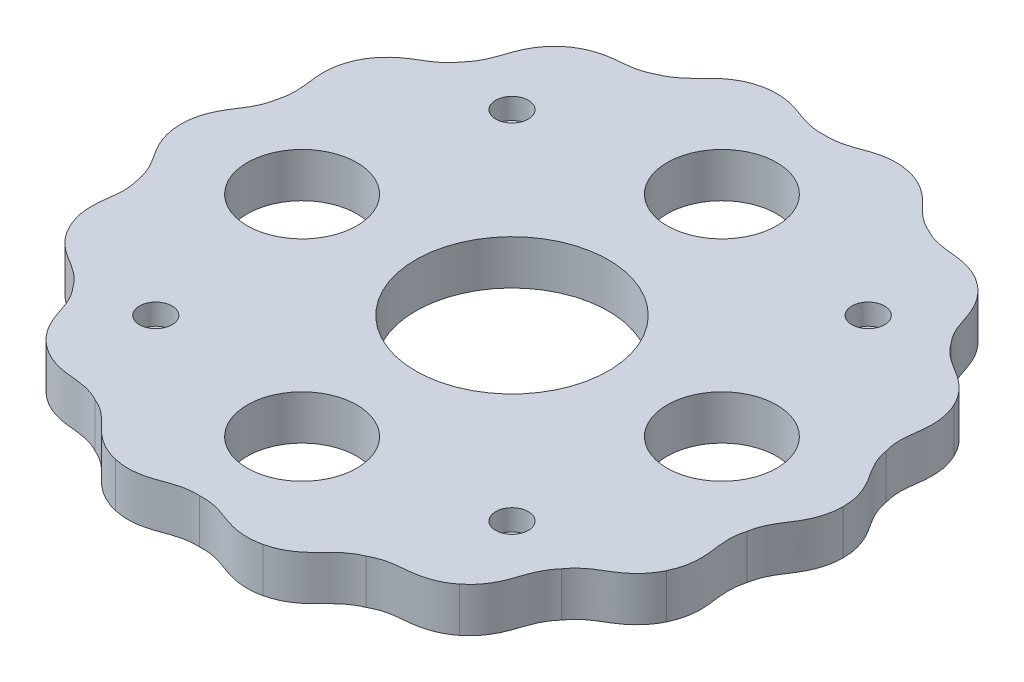
SolidWorks part; units mm, degrees
ref_plane "Front Plane" through (0, 0, 0) normal (0, 0, 1) x (1, 0, 0)
ref_plane "Top Plane" through (0, 0, 0) normal (0, 1, 0) x (1, 0, 0)
ref_plane "Right Plane" through (0, 0, 0) normal (1, 0, 0) x (0, 0, -1)
sketch "Sketch1" plane through (0, 0, 0) normal (0, 1, 0) x (1, 0, 0)
  line L0 (0, 0) -> (37.5, 0) construction
  line L1 (0, 0) -> (37.4807, 1.2019) construction
  line L2 (0, 0) -> (37.423, 2.4026) construction
  line L3 (0, 0) -> (37.3267, 3.6009) construction
  line L4 (0, 0) -> (37.1921, 4.7954) construction
  line L5 (0, 0) -> (37.0193, 5.985) construction
  line L6 (0, 0) -> (36.8085, 7.1684) construction
  line L7 (0, 0) -> (36.5598, 8.3445) construction
  line L8 (0, 0) -> (36.2736, 9.512) construction
  line L9 (0, 0) -> (35.95, 10.6698) construction
  line L10 (0, 0) -> (35.5896, 11.8166) construction
  line L11 (0, 0) -> (35.1926, 12.9512) construction
  line L12 (0, 0) -> (34.7594, 14.0725) construction
  line L13 (0, 0) -> (34.2905, 15.1794) construction
  line L14 (0, 0) -> (33.7863, 16.2706) construction
  line L15 (37.5, 0) -> (38.5, 0) construction
  line L16 (37.4807, 1.2019) -> (38.3521, 1.6927) construction
  line L17 (37.423, 2.4026) -> (37.9413, 3.2578) construction
  line L18 (37.3267, 3.6009) -> (37.3588, 4.6003) construction
  line L19 (37.1921, 4.7954) -> (36.7296, 5.682) construction
  line L20 (37.0193, 5.985) -> (36.1812, 6.5305) construction
  line L21 (36.8085, 7.1684) -> (35.8105, 7.2325) construction
  line L22 (36.5598, 8.3445) -> (35.5849, 8.122) construction
  line L23 (37, 0.0019) -> (37, 0)
  line L24 (33.3367, 16.052) -> (33.3358, 16.0537)
  line L25 (37, -0.0019) -> (37, 0)
  line L26 (33.3367, -16.052) -> (33.3358, -16.0537)
  line L27 (33.335, -16.0554) -> (33.3358, -16.0537)
  line L28 (23.0706, -28.9266) -> (23.0691, -28.9278)
  line L29 (23.0677, -28.9289) -> (23.0691, -28.9278)
  line L30 (8.2351, -36.0719) -> (8.2333, -36.0723)
  line L31 (8.2315, -36.0727) -> (8.2333, -36.0723)
  line L32 (-8.2315, -36.0727) -> (-8.2333, -36.0723)
  line L33 (-8.2351, -36.0719) -> (-8.2333, -36.0723)
  line L34 (-23.0677, -28.9289) -> (-23.0691, -28.9278)
  line L35 (-23.0706, -28.9266) -> (-23.0691, -28.9278)
  line L36 (-33.335, -16.0554) -> (-33.3358, -16.0537)
  line L37 (-33.3367, -16.052) -> (-33.3358, -16.0537)
  line L38 (-37, -0.0019) -> (-37, 0)
  line L39 (-37, 0.0019) -> (-37, 0)
  line L40 (-33.3367, 16.052) -> (-33.3358, 16.0537)
  line L41 (-33.335, 16.0554) -> (-33.3358, 16.0537)
  line L42 (-23.0706, 28.9266) -> (-23.0691, 28.9278)
  line L43 (-23.0677, 28.9289) -> (-23.0691, 28.9278)
  line L44 (-8.2351, 36.0719) -> (-8.2333, 36.0723)
  line L45 (-8.2315, 36.0727) -> (-8.2333, 36.0723)
  line L46 (8.2315, 36.0727) -> (8.2333, 36.0723)
  line L47 (8.2351, 36.0719) -> (8.2333, 36.0723)
  line L48 (23.0677, 28.9289) -> (23.0691, 28.9278)
  line L49 (23.0706, 28.9266) -> (23.0691, 28.9278)
  line L50 (33.335, 16.0554) -> (33.3358, 16.0537)
  line L51 (35.5, 0.0037) -> (35.5, 0)
  line L52 (31.986, 15.3995) -> (31.9844, 15.4029)
  line L53 (35.5, -0.0037) -> (35.5, 0)
  line L54 (31.986, -15.3995) -> (31.9844, -15.4029)
  line L55 (31.9828, -15.4062) -> (31.9844, -15.4029)
  line L56 (22.1368, -27.7527) -> (22.1339, -27.755)
  line L57 (22.131, -27.7573) -> (22.1339, -27.755)
  line L58 (7.9031, -34.6091) -> (7.8995, -34.6099)
  line L59 (7.8959, -34.6108) -> (7.8995, -34.6099)
  line L60 (-7.8959, -34.6108) -> (-7.8995, -34.6099)
  line L61 (-7.9031, -34.6091) -> (-7.8995, -34.6099)
  line L62 (-22.131, -27.7573) -> (-22.1339, -27.755)
  line L63 (-22.1368, -27.7527) -> (-22.1339, -27.755)
  line L64 (-31.9828, -15.4062) -> (-31.9844, -15.4029)
  line L65 (-31.986, -15.3995) -> (-31.9844, -15.4029)
  line L66 (-35.5, -0.0037) -> (-35.5, 0)
  line L67 (-35.5, 0.0037) -> (-35.5, 0)
  line L68 (-31.986, 15.3995) -> (-31.9844, 15.4029)
  line L69 (-31.9828, 15.4062) -> (-31.9844, 15.4029)
  line L70 (-22.1368, 27.7527) -> (-22.1339, 27.755)
  line L71 (-22.131, 27.7573) -> (-22.1339, 27.755)
  line L72 (-7.9031, 34.6091) -> (-7.8995, 34.6099)
  line L73 (-7.8959, 34.6108) -> (-7.8995, 34.6099)
  line L74 (7.8959, 34.6108) -> (7.8995, 34.6099)
  line L75 (7.9031, 34.6091) -> (7.8995, 34.6099)
  line L76 (22.131, 27.7573) -> (22.1339, 27.755)
  line L77 (22.1368, 27.7527) -> (22.1339, 27.755)
  line L78 (31.9828, 15.4062) -> (31.9844, 15.4029)
  circle A0 centre (0, 0) radius 35 construction
  circle A1 centre (37.5, 0) radius 2.5 construction
  circle A2 centre (0, 0) radius 37.5 construction
  spline S0 degree 3 poles (35.5849, 8.122) (35.6266, 7.5364) (36.0345, 6.7125) (36.7836, 5.6218) (37.4152, 4.5501) (38.2239, 2.702) (38.5014, 1.1074) (38.5, 0) knots 0 0 0 0 0.195516 0.310928 0.453873 0.621058 1 1 1 1
  spline S1 degree 3 poles (35.5849, 8.122) (35.3683, 8.6678) (35.3784, 9.5871) (35.5801, 10.8948) (35.6841, 12.1344) (35.611, 14.1503) (35.169, 15.7074) (34.6873, 16.7045) knots 0 0 0 0 0.195516 0.310928 0.453873 0.621058 1 1 1 1
  spline S2 degree 1 poles (34.1119, 7.7858) (33.3367, 16.052) knots 0 0 1 1 construction
  spline S3 degree 1 poles (34.1119, 7.7858) (37, 0.0019) knots 0 0 1 1 construction
  spline S4 degree 3 poles (33.3367, 16.052) (33.6005, 15.5058) (33.9037, 14.6401) (34.1146, 13.4372) (34.174, 12.5211) (34.1413, 11.5771) (34.0239, 10.6392) (33.8823, 9.6155) (33.9055, 8.625) (34.0243, 8.0514) (34.1119, 7.7858) knots 0.015853 0.015853 0.015853 0.015853 0.26189 0.384908 0.507927 0.630945 0.753963 0.876982 0.938491 1 1 1 1
  spline S5 degree 3 poles (34.1119, 7.7858) (34.1483, 7.5085) (34.2901, 6.9402) (34.6989, 6.0377) (35.2706, 5.1769) (35.7834, 4.3828) (36.2224, 3.5464) (36.5664, 2.6953) (36.8983, 1.52) (37.0008, 0.6085) (37, 0.0019) knots 0.015853 0.015853 0.015853 0.015853 0.077362 0.138872 0.26189 0.384908 0.507927 0.630945 0.753963 1 1 1 1
  spline S6 degree 3 poles (37, -0.0019) (37.0008, -0.6085) (36.8983, -1.52) (36.5664, -2.6953) (36.2224, -3.5464) (35.7834, -4.3828) (35.2706, -5.1769) (34.6989, -6.0377) (34.2901, -6.9402) (34.1483, -7.5085) (34.1119, -7.7858) knots 0.015853 0.015853 0.015853 0.015853 0.26189 0.384908 0.507927 0.630945 0.753963 0.876982 0.938491 1 1 1 1
  spline S7 degree 3 poles (34.1119, -7.7858) (34.0243, -8.0514) (33.9055, -8.625) (33.8823, -9.6155) (34.0239, -10.6392) (34.1413, -11.5771) (34.174, -12.5211) (34.1146, -13.4372) (33.9037, -14.6401) (33.6005, -15.5058) (33.3367, -16.052) knots 0.015853 0.015853 0.015853 0.015853 0.077362 0.138872 0.26189 0.384908 0.507927 0.630945 0.753963 1 1 1 1
  spline S8 degree 3 poles (33.335, -16.0554) (33.0725, -16.6022) (32.5847, -17.3791) (31.7758, -18.2939) (31.0965, -18.9115) (30.3381, -19.4746) (29.5316, -19.9675) (28.6429, -20.4951) (27.8831, -21.1308) (27.5087, -21.5813) (27.3556, -21.8154) knots 0.015853 0.015853 0.015853 0.015853 0.26189 0.384908 0.507927 0.630945 0.753963 0.876982 0.938491 1 1 1 1
  spline S9 degree 3 poles (27.3556, -21.8154) (27.1615, -22.0167) (26.8056, -22.4819) (26.3549, -23.3642) (26.0383, -24.348) (25.7371, -25.2439) (25.357, -26.1087) (24.906, -26.9083) (24.1941, -27.9005) (23.5453, -28.549) (23.0706, -28.9266) knots 0.015853 0.015853 0.015853 0.015853 0.077362 0.138872 0.26189 0.384908 0.507927 0.630945 0.753963 1 1 1 1
  spline S10 degree 3 poles (23.0677, -28.9289) (22.5939, -29.3077) (21.8173, -29.796) (20.6915, -30.2693) (19.8116, -30.531) (18.884, -30.7092) (17.9435, -30.8034) (16.9139, -30.8931) (15.9535, -31.1362) (15.4207, -31.3797) (15.1812, -31.5241) knots 0.015853 0.015853 0.015853 0.015853 0.26189 0.384908 0.507927 0.630945 0.753963 0.876982 0.938491 1 1 1 1
  spline S11 degree 3 poles (15.1812, -31.5241) (14.919, -31.6213) (14.3964, -31.886) (13.6076, -32.4854) (12.8955, -33.2344) (12.2354, -33.9109) (11.5177, -34.5251) (10.7645, -35.0499) (9.6926, -35.6349) (8.8266, -35.9377) (8.2351, -36.0719) knots 0.015853 0.015853 0.015853 0.015853 0.077362 0.138872 0.26189 0.384908 0.507927 0.630945 0.753963 1 1 1 1
  spline S12 degree 3 poles (8.2315, -36.0727) (7.6402, -36.2085) (6.7287, -36.3114) (5.5091, -36.2494) (4.6028, -36.1034) (3.6897, -35.8614) (2.8014, -35.5383) (1.8349, -35.1724) (0.8641, -34.9747) (0.2785, -34.9629) (0, -34.9891) knots 0.015853 0.015853 0.015853 0.015853 0.26189 0.384908 0.507927 0.630945 0.753963 0.876982 0.938491 1 1 1 1
  spline S13 degree 3 poles (0, -34.9891) (-0.2785, -34.9629) (-0.8641, -34.9747) (-1.8349, -35.1724) (-2.8014, -35.5383) (-3.6897, -35.8614) (-4.6028, -36.1034) (-5.5091, -36.2494) (-6.7287, -36.3114) (-7.6402, -36.2085) (-8.2315, -36.0727) knots 0.015853 0.015853 0.015853 0.015853 0.077362 0.138872 0.26189 0.384908 0.507927 0.630945 0.753963 1 1 1 1
  spline S14 degree 3 poles (-8.2351, -36.0719) (-8.8266, -35.9377) (-9.6926, -35.6349) (-10.7645, -35.0499) (-11.5177, -34.5251) (-12.2354, -33.9109) (-12.8955, -33.2344) (-13.6076, -32.4854) (-14.3964, -31.886) (-14.919, -31.6213) (-15.1812, -31.5241) knots 0.015853 0.015853 0.015853 0.015853 0.26189 0.384908 0.507927 0.630945 0.753963 0.876982 0.938491 1 1 1 1
  spline S15 degree 3 poles (-15.1812, -31.5241) (-15.4207, -31.3797) (-15.9535, -31.1362) (-16.9139, -30.8931) (-17.9435, -30.8034) (-18.884, -30.7092) (-19.8116, -30.531) (-20.6915, -30.2693) (-21.8173, -29.796) (-22.5939, -29.3077) (-23.0677, -28.9289) knots 0.015853 0.015853 0.015853 0.015853 0.077362 0.138872 0.26189 0.384908 0.507927 0.630945 0.753963 1 1 1 1
  spline S16 degree 3 poles (-23.0706, -28.9266) (-23.5453, -28.549) (-24.1941, -27.9005) (-24.906, -26.9083) (-25.357, -26.1087) (-25.7371, -25.2439) (-26.0383, -24.348) (-26.3549, -23.3642) (-26.8056, -22.4819) (-27.1615, -22.0167) (-27.3556, -21.8154) knots 0.015853 0.015853 0.015853 0.015853 0.26189 0.384908 0.507927 0.630945 0.753963 0.876982 0.938491 1 1 1 1
  spline S17 degree 3 poles (-27.3556, -21.8154) (-27.5087, -21.5813) (-27.8831, -21.1308) (-28.6429, -20.4951) (-29.5316, -19.9675) (-30.3381, -19.4746) (-31.0965, -18.9115) (-31.7758, -18.2939) (-32.5847, -17.3791) (-33.0725, -16.6022) (-33.335, -16.0554) knots 0.015853 0.015853 0.015853 0.015853 0.077362 0.138872 0.26189 0.384908 0.507927 0.630945 0.753963 1 1 1 1
  spline S18 degree 3 poles (-33.3367, -16.052) (-33.6005, -15.5058) (-33.9037, -14.6401) (-34.1146, -13.4372) (-34.174, -12.5211) (-34.1413, -11.5771) (-34.0239, -10.6392) (-33.8823, -9.6155) (-33.9055, -8.625) (-34.0243, -8.0514) (-34.1119, -7.7858) knots 0.015853 0.015853 0.015853 0.015853 0.26189 0.384908 0.507927 0.630945 0.753963 0.876982 0.938491 1 1 1 1
  spline S19 degree 3 poles (-34.1119, -7.7858) (-34.1483, -7.5085) (-34.2901, -6.9402) (-34.6989, -6.0377) (-35.2706, -5.1769) (-35.7834, -4.3828) (-36.2224, -3.5464) (-36.5664, -2.6953) (-36.8983, -1.52) (-37.0008, -0.6085) (-37, -0.0019) knots 0.015853 0.015853 0.015853 0.015853 0.077362 0.138872 0.26189 0.384908 0.507927 0.630945 0.753963 1 1 1 1
  spline S20 degree 3 poles (-37, 0.0019) (-37.0008, 0.6085) (-36.8983, 1.52) (-36.5664, 2.6953) (-36.2224, 3.5464) (-35.7834, 4.3828) (-35.2706, 5.1769) (-34.6989, 6.0377) (-34.2901, 6.9402) (-34.1483, 7.5085) (-34.1119, 7.7858) knots 0.015853 0.015853 0.015853 0.015853 0.26189 0.384908 0.507927 0.630945 0.753963 0.876982 0.938491 1 1 1 1
  spline S21 degree 3 poles (-34.1119, 7.7858) (-34.0243, 8.0514) (-33.9055, 8.625) (-33.8823, 9.6155) (-34.0239, 10.6392) (-34.1413, 11.5771) (-34.174, 12.5211) (-34.1146, 13.4372) (-33.9037, 14.6401) (-33.6005, 15.5058) (-33.3367, 16.052) knots 0.015853 0.015853 0.015853 0.015853 0.077362 0.138872 0.26189 0.384908 0.507927 0.630945 0.753963 1 1 1 1
  spline S22 degree 3 poles (-33.335, 16.0554) (-33.0725, 16.6022) (-32.5847, 17.3791) (-31.7758, 18.2939) (-31.0965, 18.9115) (-30.3381, 19.4746) (-29.5316, 19.9675) (-28.6429, 20.4951) (-27.8831, 21.1308) (-27.5087, 21.5813) (-27.3556, 21.8154) knots 0.015853 0.015853 0.015853 0.015853 0.26189 0.384908 0.507927 0.630945 0.753963 0.876982 0.938491 1 1 1 1
  spline S23 degree 3 poles (-27.3556, 21.8154) (-27.1615, 22.0167) (-26.8056, 22.4819) (-26.3549, 23.3642) (-26.0383, 24.348) (-25.7371, 25.2439) (-25.357, 26.1087) (-24.906, 26.9083) (-24.1941, 27.9005) (-23.5453, 28.549) (-23.0706, 28.9266) knots 0.015853 0.015853 0.015853 0.015853 0.077362 0.138872 0.26189 0.384908 0.507927 0.630945 0.753963 1 1 1 1
  spline S24 degree 3 poles (-23.0677, 28.9289) (-22.5939, 29.3077) (-21.8173, 29.796) (-20.6915, 30.2693) (-19.8116, 30.531) (-18.884, 30.7092) (-17.9435, 30.8034) (-16.9139, 30.8931) (-15.9535, 31.1362) (-15.4207, 31.3797) (-15.1812, 31.5241) knots 0.015853 0.015853 0.015853 0.015853 0.26189 0.384908 0.507927 0.630945 0.753963 0.876982 0.938491 1 1 1 1
  spline S25 degree 3 poles (-15.1812, 31.5241) (-14.919, 31.6213) (-14.3964, 31.886) (-13.6076, 32.4854) (-12.8955, 33.2344) (-12.2354, 33.9109) (-11.5177, 34.5251) (-10.7645, 35.0499) (-9.6926, 35.6349) (-8.8266, 35.9377) (-8.2351, 36.0719) knots 0.015853 0.015853 0.015853 0.015853 0.077362 0.138872 0.26189 0.384908 0.507927 0.630945 0.753963 1 1 1 1
  spline S26 degree 3 poles (-8.2315, 36.0727) (-7.6402, 36.2085) (-6.7287, 36.3114) (-5.5091, 36.2494) (-4.6028, 36.1034) (-3.6897, 35.8614) (-2.8014, 35.5383) (-1.8349, 35.1724) (-0.8641, 34.9747) (-0.2785, 34.9629) (0, 34.9891) knots 0.015853 0.015853 0.015853 0.015853 0.26189 0.384908 0.507927 0.630945 0.753963 0.876982 0.938491 1 1 1 1
  spline S27 degree 3 poles (0, 34.9891) (0.2785, 34.9629) (0.8641, 34.9747) (1.8349, 35.1724) (2.8014, 35.5383) (3.6897, 35.8614) (4.6028, 36.1034) (5.5091, 36.2494) (6.7287, 36.3114) (7.6402, 36.2085) (8.2315, 36.0727) knots 0.015853 0.015853 0.015853 0.015853 0.077362 0.138872 0.26189 0.384908 0.507927 0.630945 0.753963 1 1 1 1
  spline S28 degree 3 poles (8.2351, 36.0719) (8.8266, 35.9377) (9.6926, 35.6349) (10.7645, 35.0499) (11.5177, 34.5251) (12.2354, 33.9109) (12.8955, 33.2344) (13.6076, 32.4854) (14.3964, 31.886) (14.919, 31.6213) (15.1812, 31.5241) knots 0.015853 0.015853 0.015853 0.015853 0.26189 0.384908 0.507927 0.630945 0.753963 0.876982 0.938491 1 1 1 1
  spline S29 degree 3 poles (15.1812, 31.5241) (15.4207, 31.3797) (15.9535, 31.1362) (16.9139, 30.8931) (17.9435, 30.8034) (18.884, 30.7092) (19.8116, 30.531) (20.6915, 30.2693) (21.8173, 29.796) (22.5939, 29.3077) (23.0677, 28.9289) knots 0.015853 0.015853 0.015853 0.015853 0.077362 0.138872 0.26189 0.384908 0.507927 0.630945 0.753963 1 1 1 1
  spline S30 degree 3 poles (23.0706, 28.9266) (23.5453, 28.549) (24.1941, 27.9005) (24.906, 26.9083) (25.357, 26.1087) (25.7371, 25.2439) (26.0383, 24.348) (26.3549, 23.3642) (26.8056, 22.4819) (27.1615, 22.0167) (27.3556, 21.8154) knots 0.015853 0.015853 0.015853 0.015853 0.26189 0.384908 0.507927 0.630945 0.753963 0.876982 0.938491 1 1 1 1
  spline S31 degree 3 poles (27.3556, 21.8154) (27.5087, 21.5813) (27.8831, 21.1308) (28.6429, 20.4951) (29.5316, 19.9675) (30.3381, 19.4746) (31.0965, 18.9115) (31.7758, 18.2939) (32.5847, 17.3791) (33.0725, 16.6022) (33.335, 16.0554) knots 0.015853 0.015853 0.015853 0.015853 0.077362 0.138872 0.26189 0.384908 0.507927 0.630945 0.753963 1 1 1 1
  spline S32 degree 1 poles (32.6448, 7.451) (35.5, 0.0037) knots 0 0 1 1 construction
  spline S33 degree 1 poles (32.6448, 7.451) (31.986, 15.3995) knots 0 0 1 1 construction
  spline S34 degree 3 poles (35.5, 0.0037) (35.5006, 0.4959) (35.4183, 1.2336) (35.1496, 2.1927) (34.8707, 2.8896) (34.4997, 3.6015) (34.1394, 4.1652) (33.6939, 4.8394) (33.3068, 5.4873) (32.9751, 6.1975) (32.758, 6.8733) (32.6748, 7.2607) (32.6448, 7.451) knots 0.023011 0.023011 0.023011 0.023011 0.267258 0.389382 0.511505 0.633629 0.755753 0.816814 0.877876 0.938938 0.969469 1 1 1 1
  spline S35 degree 3 poles (32.6448, 7.451) (32.5893, 7.6354) (32.4961, 8.0206) (32.3985, 8.7236) (32.3893, 9.5074) (32.4569, 10.2591) (32.5657, 11.0598) (32.6458, 11.724) (32.6712, 12.5264) (32.6201, 13.2752) (32.446, 14.256) (32.2001, 14.9563) (31.986, 15.3995) knots 0.023011 0.023011 0.023011 0.023011 0.053542 0.084072 0.145134 0.206196 0.267258 0.389382 0.511505 0.633629 0.755753 1 1 1 1
  spline S36 degree 3 poles (32.6448, -7.451) (32.6748, -7.2607) (32.758, -6.8733) (32.9751, -6.1975) (33.3068, -5.4873) (33.6939, -4.8394) (34.1394, -4.1652) (34.4997, -3.6015) (34.8707, -2.8896) (35.1496, -2.1927) (35.4183, -1.2336) (35.5006, -0.4959) (35.5, -0.0037) knots 0.023011 0.023011 0.023011 0.023011 0.053542 0.084072 0.145134 0.206196 0.267258 0.389382 0.511505 0.633629 0.755753 1 1 1 1
  spline S37 degree 3 poles (31.986, -15.3995) (32.2001, -14.9563) (32.446, -14.256) (32.6201, -13.2752) (32.6712, -12.5264) (32.6458, -11.724) (32.5657, -11.0598) (32.4569, -10.2591) (32.3893, -9.5074) (32.3985, -8.7236) (32.4961, -8.0206) (32.5893, -7.6354) (32.6448, -7.451) knots 0.023011 0.023011 0.023011 0.023011 0.267258 0.389382 0.511505 0.633629 0.755753 0.816814 0.877876 0.938938 0.969469 1 1 1 1
  spline S38 degree 3 poles (26.1791, -20.8771) (26.2887, -20.7187) (26.5317, -20.4057) (27.0205, -19.8911) (27.6275, -19.3952) (28.2574, -18.9793) (28.9513, -18.5652) (29.5206, -18.2137) (30.1637, -17.7333) (30.7173, -17.2264) (31.3755, -16.4789) (31.7698, -15.8499) (31.9828, -15.4062) knots 0.023011 0.023011 0.023011 0.023011 0.053542 0.084072 0.145134 0.206196 0.267258 0.389382 0.511505 0.633629 0.755753 1 1 1 1
  spline S39 degree 3 poles (22.1368, -27.7527) (22.522, -27.4463) (23.0474, -26.922) (23.6297, -26.1139) (24.0007, -25.4614) (24.326, -24.7275) (24.542, -24.0943) (24.7914, -23.3257) (25.0566, -22.619) (25.405, -21.9169) (25.798, -21.3258) (26.0491, -21.0192) (26.1791, -20.8771) knots 0.023011 0.023011 0.023011 0.023011 0.267258 0.389382 0.511505 0.633629 0.755753 0.816814 0.877876 0.938938 0.969469 1 1 1 1
  spline S40 degree 3 poles (14.5283, -30.1683) (14.6957, -30.0732) (15.0505, -29.8966) (15.7143, -29.645) (16.4763, -29.4616) (17.2242, -29.3602) (18.0291, -29.2882) (18.6945, -29.2185) (19.4823, -29.0647) (20.201, -28.8482) (21.1184, -28.4603) (21.7465, -28.0647) (22.131, -27.7573) knots 0.023011 0.023011 0.023011 0.023011 0.053542 0.084072 0.145134 0.206196 0.267258 0.389382 0.511505 0.633629 0.755753 1 1 1 1
  spline S41 degree 3 poles (7.9031, -34.6091) (8.3831, -34.5002) (9.084, -34.2557) (9.9593, -33.7804) (10.5766, -33.3534) (11.1881, -32.8334) (11.6575, -32.3566) (12.2156, -31.7723) (12.7612, -31.2507) (13.3797, -30.7693) (13.9903, -30.4072) (14.3495, -30.2399) (14.5283, -30.1683) knots 0.023011 0.023011 0.023011 0.023011 0.267258 0.389382 0.511505 0.633629 0.755753 0.816814 0.877876 0.938938 0.969469 1 1 1 1
  spline S42 degree 3 poles (0, -33.4843) (0.1922, -33.4712) (0.5884, -33.4661) (1.2956, -33.5274) (2.0617, -33.6928) (2.7796, -33.926) (3.536, -34.2103) (4.1657, -34.4362) (4.9423, -34.6394) (5.6838, -34.7562) (6.6786, -34.8048) (7.4161, -34.7209) (7.8959, -34.6108) knots 0.023011 0.023011 0.023011 0.023011 0.053542 0.084072 0.145134 0.206196 0.267258 0.389382 0.511505 0.633629 0.755753 1 1 1 1
  spline S43 degree 3 poles (-7.8959, -34.6108) (-7.4161, -34.7209) (-6.6786, -34.8048) (-5.6838, -34.7562) (-4.9423, -34.6394) (-4.1657, -34.4362) (-3.536, -34.2103) (-2.7796, -33.926) (-2.0617, -33.6928) (-1.2956, -33.5274) (-0.5884, -33.4661) (-0.1922, -33.4712) (0, -33.4843) knots 0.023011 0.023011 0.023011 0.023011 0.267258 0.389382 0.511505 0.633629 0.755753 0.816814 0.877876 0.938938 0.969469 1 1 1 1
  spline S44 degree 3 poles (-14.5283, -30.1683) (-14.3495, -30.2399) (-13.9903, -30.4072) (-13.3797, -30.7693) (-12.7612, -31.2507) (-12.2156, -31.7723) (-11.6575, -32.3566) (-11.1881, -32.8334) (-10.5766, -33.3534) (-9.9593, -33.7804) (-9.084, -34.2557) (-8.3831, -34.5002) (-7.9031, -34.6091) knots 0.023011 0.023011 0.023011 0.023011 0.053542 0.084072 0.145134 0.206196 0.267258 0.389382 0.511505 0.633629 0.755753 1 1 1 1
  spline S45 degree 3 poles (-22.131, -27.7573) (-21.7465, -28.0647) (-21.1184, -28.4603) (-20.201, -28.8482) (-19.4823, -29.0647) (-18.6945, -29.2185) (-18.0291, -29.2882) (-17.2242, -29.3602) (-16.4763, -29.4616) (-15.7143, -29.645) (-15.0505, -29.8966) (-14.6957, -30.0732) (-14.5283, -30.1683) knots 0.023011 0.023011 0.023011 0.023011 0.267258 0.389382 0.511505 0.633629 0.755753 0.816814 0.877876 0.938938 0.969469 1 1 1 1
  spline S46 degree 3 poles (-26.1791, -20.8771) (-26.0491, -21.0192) (-25.798, -21.3258) (-25.405, -21.9169) (-25.0566, -22.619) (-24.7914, -23.3257) (-24.542, -24.0943) (-24.326, -24.7275) (-24.0007, -25.4614) (-23.6297, -26.1139) (-23.0474, -26.922) (-22.522, -27.4463) (-22.1368, -27.7527) knots 0.023011 0.023011 0.023011 0.023011 0.053542 0.084072 0.145134 0.206196 0.267258 0.389382 0.511505 0.633629 0.755753 1 1 1 1
  spline S47 degree 3 poles (-31.9828, -15.4062) (-31.7698, -15.8499) (-31.3755, -16.4789) (-30.7173, -17.2264) (-30.1637, -17.7333) (-29.5206, -18.2137) (-28.9513, -18.5652) (-28.2574, -18.9793) (-27.6275, -19.3952) (-27.0205, -19.8911) (-26.5317, -20.4057) (-26.2887, -20.7187) (-26.1791, -20.8771) knots 0.023011 0.023011 0.023011 0.023011 0.267258 0.389382 0.511505 0.633629 0.755753 0.816814 0.877876 0.938938 0.969469 1 1 1 1
  spline S48 degree 3 poles (-32.6448, -7.451) (-32.5893, -7.6354) (-32.4961, -8.0206) (-32.3985, -8.7236) (-32.3893, -9.5074) (-32.4569, -10.2591) (-32.5657, -11.0598) (-32.6458, -11.724) (-32.6712, -12.5264) (-32.6201, -13.2752) (-32.446, -14.256) (-32.2001, -14.9563) (-31.986, -15.3995) knots 0.023011 0.023011 0.023011 0.023011 0.053542 0.084072 0.145134 0.206196 0.267258 0.389382 0.511505 0.633629 0.755753 1 1 1 1
  spline S49 degree 3 poles (-35.5, -0.0037) (-35.5006, -0.4959) (-35.4183, -1.2336) (-35.1496, -2.1927) (-34.8707, -2.8896) (-34.4997, -3.6015) (-34.1394, -4.1652) (-33.6939, -4.8394) (-33.3068, -5.4873) (-32.9751, -6.1975) (-32.758, -6.8733) (-32.6748, -7.2607) (-32.6448, -7.451) knots 0.023011 0.023011 0.023011 0.023011 0.267258 0.389382 0.511505 0.633629 0.755753 0.816814 0.877876 0.938938 0.969469 1 1 1 1
  spline S50 degree 3 poles (-32.6448, 7.451) (-32.6748, 7.2607) (-32.758, 6.8733) (-32.9751, 6.1975) (-33.3068, 5.4873) (-33.6939, 4.8394) (-34.1394, 4.1652) (-34.4997, 3.6015) (-34.8707, 2.8896) (-35.1496, 2.1927) (-35.4183, 1.2336) (-35.5006, 0.4959) (-35.5, 0.0037) knots 0.023011 0.023011 0.023011 0.023011 0.053542 0.084072 0.145134 0.206196 0.267258 0.389382 0.511505 0.633629 0.755753 1 1 1 1
  spline S51 degree 3 poles (-31.986, 15.3995) (-32.2001, 14.9563) (-32.446, 14.256) (-32.6201, 13.2752) (-32.6712, 12.5264) (-32.6458, 11.724) (-32.5657, 11.0598) (-32.4569, 10.2591) (-32.3893, 9.5074) (-32.3985, 8.7236) (-32.4961, 8.0206) (-32.5893, 7.6354) (-32.6448, 7.451) knots 0.023011 0.023011 0.023011 0.023011 0.267258 0.389382 0.511505 0.633629 0.755753 0.816814 0.877876 0.938938 0.969469 1 1 1 1
  spline S52 degree 3 poles (-26.1791, 20.8771) (-26.2887, 20.7187) (-26.5317, 20.4057) (-27.0205, 19.8911) (-27.6275, 19.3952) (-28.2574, 18.9793) (-28.9513, 18.5652) (-29.5206, 18.2137) (-30.1637, 17.7333) (-30.7173, 17.2264) (-31.3755, 16.4789) (-31.7698, 15.8499) (-31.9828, 15.4062) knots 0.023011 0.023011 0.023011 0.023011 0.053542 0.084072 0.145134 0.206196 0.267258 0.389382 0.511505 0.633629 0.755753 1 1 1 1
  spline S53 degree 3 poles (-22.1368, 27.7527) (-22.522, 27.4463) (-23.0474, 26.922) (-23.6297, 26.1139) (-24.0007, 25.4614) (-24.326, 24.7275) (-24.542, 24.0943) (-24.7914, 23.3257) (-25.0566, 22.619) (-25.405, 21.9169) (-25.798, 21.3258) (-26.0491, 21.0192) (-26.1791, 20.8771) knots 0.023011 0.023011 0.023011 0.023011 0.267258 0.389382 0.511505 0.633629 0.755753 0.816814 0.877876 0.938938 0.969469 1 1 1 1
  spline S54 degree 3 poles (-14.5283, 30.1683) (-14.6957, 30.0732) (-15.0505, 29.8966) (-15.7143, 29.645) (-16.4763, 29.4616) (-17.2242, 29.3602) (-18.0291, 29.2882) (-18.6945, 29.2185) (-19.4823, 29.0647) (-20.201, 28.8482) (-21.1184, 28.4603) (-21.7465, 28.0647) (-22.131, 27.7573) knots 0.023011 0.023011 0.023011 0.023011 0.053542 0.084072 0.145134 0.206196 0.267258 0.389382 0.511505 0.633629 0.755753 1 1 1 1
  spline S55 degree 3 poles (-7.9031, 34.6091) (-8.3831, 34.5002) (-9.084, 34.2557) (-9.9593, 33.7804) (-10.5766, 33.3534) (-11.1881, 32.8334) (-11.6575, 32.3566) (-12.2156, 31.7723) (-12.7612, 31.2507) (-13.3797, 30.7693) (-13.9903, 30.4072) (-14.3495, 30.2399) (-14.5283, 30.1683) knots 0.023011 0.023011 0.023011 0.023011 0.267258 0.389382 0.511505 0.633629 0.755753 0.816814 0.877876 0.938938 0.969469 1 1 1 1
  spline S56 degree 3 poles (0, 33.4843) (-0.1922, 33.4712) (-0.5884, 33.4661) (-1.2956, 33.5274) (-2.0617, 33.6928) (-2.7796, 33.926) (-3.536, 34.2103) (-4.1657, 34.4362) (-4.9423, 34.6394) (-5.6838, 34.7562) (-6.6786, 34.8048) (-7.4161, 34.7209) (-7.8959, 34.6108) knots 0.023011 0.023011 0.023011 0.023011 0.053542 0.084072 0.145134 0.206196 0.267258 0.389382 0.511505 0.633629 0.755753 1 1 1 1
  spline S57 degree 3 poles (7.8959, 34.6108) (7.4161, 34.7209) (6.6786, 34.8048) (5.6838, 34.7562) (4.9423, 34.6394) (4.1657, 34.4362) (3.536, 34.2103) (2.7796, 33.926) (2.0617, 33.6928) (1.2956, 33.5274) (0.5884, 33.4661) (0.1922, 33.4712) (0, 33.4843) knots 0.023011 0.023011 0.023011 0.023011 0.267258 0.389382 0.511505 0.633629 0.755753 0.816814 0.877876 0.938938 0.969469 1 1 1 1
  spline S58 degree 3 poles (14.5283, 30.1683) (14.3495, 30.2399) (13.9903, 30.4072) (13.3797, 30.7693) (12.7612, 31.2507) (12.2156, 31.7723) (11.6575, 32.3566) (11.1881, 32.8334) (10.5766, 33.3534) (9.9593, 33.7804) (9.084, 34.2557) (8.3831, 34.5002) (7.9031, 34.6091) knots 0.023011 0.023011 0.023011 0.023011 0.053542 0.084072 0.145134 0.206196 0.267258 0.389382 0.511505 0.633629 0.755753 1 1 1 1
  spline S59 degree 3 poles (22.131, 27.7573) (21.7465, 28.0647) (21.1184, 28.4603) (20.201, 28.8482) (19.4823, 29.0647) (18.6945, 29.2185) (18.0291, 29.2882) (17.2242, 29.3602) (16.4763, 29.4616) (15.7143, 29.645) (15.0505, 29.8966) (14.6957, 30.0732) (14.5283, 30.1683) knots 0.023011 0.023011 0.023011 0.023011 0.267258 0.389382 0.511505 0.633629 0.755753 0.816814 0.877876 0.938938 0.969469 1 1 1 1
  spline S60 degree 3 poles (26.1791, 20.8771) (26.0491, 21.0192) (25.798, 21.3258) (25.405, 21.9169) (25.0566, 22.619) (24.7914, 23.3257) (24.542, 24.0943) (24.326, 24.7275) (24.0007, 25.4614) (23.6297, 26.1139) (23.0474, 26.922) (22.522, 27.4463) (22.1368, 27.7527) knots 0.023011 0.023011 0.023011 0.023011 0.053542 0.084072 0.145134 0.206196 0.267258 0.389382 0.511505 0.633629 0.755753 1 1 1 1
  spline S61 degree 3 poles (31.9828, 15.4062) (31.7698, 15.8499) (31.3755, 16.4789) (30.7173, 17.2264) (30.1637, 17.7333) (29.5206, 18.2137) (28.9513, 18.5652) (28.2574, 18.9793) (27.6275, 19.3952) (27.0205, 19.8911) (26.5317, 20.4057) (26.2887, 20.7187) (26.1791, 20.8771) knots 0.023011 0.023011 0.023011 0.023011 0.267258 0.389382 0.511505 0.633629 0.755753 0.816814 0.877876 0.938938 0.969469 1 1 1 1
  point P25 (0, 0)
  point P117 (0, 0)
  point P174 (0, 0)
  dimension "D1" = 70
  dimension "D2" = 5
  dimension "D4" = 25.714
  dimension "D5" = 1
  dimension "D7" = 180
  dimension "D8" = 207.551
  dimension "D6" = 1
  dimension "D9" = 1
  dimension "D10" = 235.102
  dimension "D11" = 1
  dimension "D12" = 1
  dimension "D13" = 1
  dimension "D14" = 1
  dimension "D15" = 1
  dimension "D16" = 262.653
  dimension "D17" = 290.204
  dimension "D18" = 317.755
  dimension "D19" = 345.306
  dimension "D20" = 1.5
  dimension "D22" = 3
  dimension "D3" = 15
  dimension "D21" = 14
  dimension "D23" = 14
extrude "Boss-Extrude3" add sketch "Sketch1" along normal blind 4.7625 contours L51 L53 S36 S37 L54 L55 S38 S39 L56 L57 S40 S41 L58 L59 S42 S43 L60 L61 S44 S45 L62 L63 S46 S47 L64 L65 S48 S49 L66 L67 S50 S51 L68 L69 S52 S53 L70 L71 S54 S55 L72 L73 S56 S57 L74 L75 S58 S59 L76 L77 S60 S61 L78 L52 S35 S34
sketch "Sketch2" plane through (0, 4.7625, 0) normal (0, 1, 0) x (1, 0, 0)
  line L0 (0, 0) -> (22.5, 0) construction
  line L1 (0, 0) -> (19.0919, 19.0919) construction
  circle A0 centre (0, 0) radius 10.3281
  circle A1 centre (22.5, 0) radius 5.875
  circle A6 centre (19.0919, 19.0919) radius 1.75
  circle A7 centre (0, -22.5) radius 5.875
  circle A8 centre (19.0919, -19.0919) radius 1.75
  circle A9 centre (-22.5, 0) radius 5.875
  circle A10 centre (-19.0919, -19.0919) radius 1.75
  circle A11 centre (0, 22.5) radius 5.875
  circle A12 centre (-19.0919, 19.0919) radius 1.75
  point P16 (0, 0)
  point P21 (0, 0)
  point P24 (0, 0)
  dimension "D3" = 11.75
  dimension "D1" = 20.6562
  dimension "D6" = 3.5
  dimension "D2" = 22.5
  dimension "D4" = 45
  dimension "D5" = 27
  dimension "D7" = 4
extrude "Cut-Extrude1" cut sketch "Sketch2" against normal blind 4.7625 contours A7 | A0 | A0 | A0 | L0 A0 | A0 L0 | A1 | A9 | A11 region at (22.5, 4.7625, -5.7088) region at (-10.036, 4.7625, 0) region at (0, 4.7625, 22.5) region at (-22.5, 4.7625, 0) region at (0, 4.7625, -22.5)
extrude "Cut-Extrude2" cut sketch "Sketch2<4>" against normal blind 2.2458 contours A12 | A10 | A8 | A6 region at (19.0919, 4.7625, -19.0919) region at (19.0919, 4.7625, 19.0919) region at (-19.0919, 4.7625, 19.0919) region at (-19.0919, 4.7625, -19.0919)
sketch "Sketch2<4>" plane through (0, 4.7625, 0) normal (0, 1, 0) x (1, 0, 0) same geometry as "Sketch2"
equation "\"D5@Sketch1\" = \"eccentricity\""
equation "\"D6@Sketch1\" = \"eccentricity\""
equation "\"D9@Sketch1\" = \"eccentricity\""
equation "\"D11@Sketch1\" = \"eccentricity\""
equation "\"D12@Sketch1\" = \"eccentricity\""
equation "\"D14@Sketch1\" = \"eccentricity\""
equation "\"D13@Sketch1\" = \"eccentricity\""
equation "\"D15@Sketch1\"= \"eccentricity\""
equation "\"D1@Sketch2\"=\"largeBearOD\"-\"largeBearOTight\""
equation "\"D1@Cut-Extrude2\"=\"ballBearDiam\"-(\"sheetThickness\"-1)/3"
equation "\"D1@Boss-Extrude3\"=\"sheetThickness\""
equation "\"smallBearOD\"= 14.8mm"
equation "\"smallBearID\" = 10mm"
equation "\"smallBearOTight\"= 0mm'calibrate - hold onto bottom of gearbox"
equation "\"smallBearOLoose\"= 0mm'calibrate - able to take off topHat"
equation "\"smallBearITight\" = 0mm'hold onto "
equation "\"pinCircleDiam\"= 75mm"
equation "\"pinDiam\"= 6mm"
equation "\"sheetThickness\"= 0.1875in"
equation "\"D6@Sketch2\"=\"ballBearDiam\""
equation "\"largeBearOD\"= 21mm"
equation "\"largeBearID\" = 15mm"
equation "\"largeBearOTight\"= 0.34375mm'calibrate - hold onto gears"
equation "\"largeBearITight\"= 0mm'calibrate - hold onto eccentric nut"
equation "\"ballBearDiam\"= 3.5mm"
equation "\"thrustBearingThickness\"= 5mm'measure this irl and change"
equation "\"thrustBearingID\"= 0mm'measure this irl and change"
equation "\"thrustBearingOD\"= 0mm'measure this irl and change"
equation "\"eccentricity\" = 1mm"
equation "\"D1@Cut-Extrude1\"=\"sheetThickness\""
